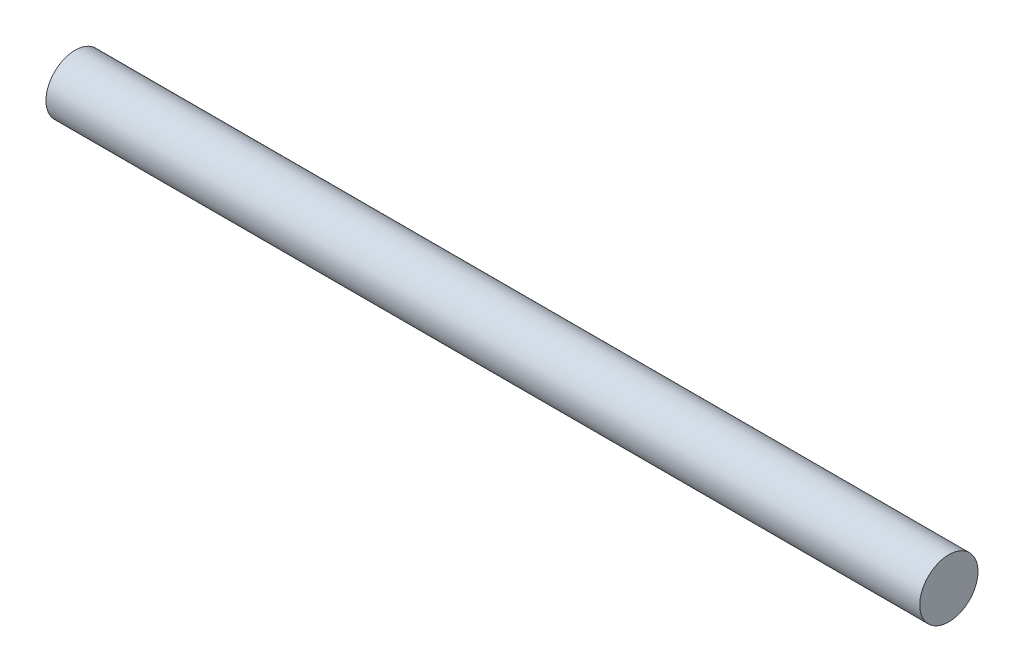
SolidWorks part; units mm, degrees
material "1060-H12"
ref_plane "Front" through (0, 0, 0) normal (0, 0, 1) x (1, 0, 0)
ref_plane "Top" through (0, 0, 0) normal (0, 1, 0) x (1, 0, 0)
ref_plane "Right" through (0, 0, 0) normal (1, 0, 0) x (0, 0, -1)
sketch "Sketch1" plane through (0, 0, 0) normal (1, 0, 0) x (0, 0, -1)
  circle A0 centre (0, 0) radius 5
extrude "Boss-Extrude1" add sketch "Sketch1" along normal blind 75 and the other way blind 75
ref_axis "Axis1" through (0, 50, 0) along (0, -1, 0)
